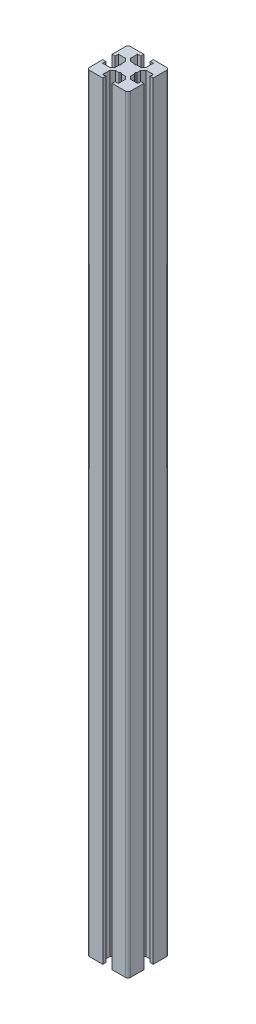
SolidWorks part; units mm, degrees
ref_plane "Front Plane" through (0, 0, 0) normal (0, 0, 1) x (1, 0, 0)
ref_plane "Top Plane" through (0, 0, 0) normal (0, 1, 0) x (1, 0, 0)
ref_plane "Right Plane" through (0, 0, 0) normal (1, 0, 0) x (0, 0, -1)
sketch "Sketch2" plane through (0, 0, 0) normal (0, 1, 0) x (1, 0, 0)
  line L3 (1.7, 7.5) -> (6.5, 7.5)
  line L5 (0, 2.5) -> (-0.5196, 2.8)
  line L6 (-2.85, 3.8) -> (-1.85, 2.8)
  line L9 (1.7, 6.4) -> (1.7, 7.5)
  line L10 (1.7, 6.4) -> (2.85, 6.4)
  line L11 (2.85, 6.4) -> (2.85, 3.8)
  line L12 (2.85, 3.8) -> (1.85, 2.8)
  line L13 (1.85, 2.8) -> (0.5196, 2.8)
  line L14 (2.8, -0.5196) -> (2.8, -1.85)
  line L15 (0, 2.5) -> (0.5196, 2.8)
  line L16 (-2.85, 6.4) -> (-2.85, 3.8)
  line L17 (-1.7, 6.4) -> (-2.85, 6.4)
  line L18 (-1.7, 6.4) -> (-1.7, 7.5)
  line L19 (-1.7, 7.5) -> (-6.5, 7.5)
  line L21 (7.5, -1.7) -> (7.5, -6.5)
  line L22 (6.4, -1.7) -> (7.5, -1.7)
  line L23 (6.4, -1.7) -> (6.4, -2.85)
  line L24 (6.4, -2.85) -> (3.8, -2.85)
  line L25 (2.5, 0) -> (2.8, 0.5196)
  line L26 (0.5196, -2.8) -> (1.85, -2.8)
  line L27 (2.8, 1.85) -> (2.8, 0.5196)
  line L28 (3.8, 2.85) -> (2.8, 1.85)
  line L29 (6.4, 2.85) -> (3.8, 2.85)
  line L30 (6.4, 1.7) -> (6.4, 2.85)
  line L31 (6.4, 1.7) -> (7.5, 1.7)
  line L32 (3.8, -2.85) -> (2.8, -1.85)
  line L33 (2.5, 0) -> (2.8, -0.5196)
  line L34 (7.5, 1.7) -> (7.5, 6.5)
  line L36 (-1.7, -6.4) -> (-1.7, -7.5)
  line L37 (0, -2.5) -> (0.5196, -2.8)
  line L38 (2.85, -3.8) -> (1.85, -2.8)
  line L39 (-1.85, -2.8) -> (-0.5196, -2.8)
  line L41 (0, -2.5) -> (-0.5196, -2.8)
  line L42 (2.85, -6.4) -> (2.85, -3.8)
  line L43 (1.7, -6.4) -> (2.85, -6.4)
  line L44 (1.7, -6.4) -> (1.7, -7.5)
  line L45 (1.7, -7.5) -> (6.5, -7.5)
  line L46 (-1.7, -7.5) -> (-6.5, -7.5)
  line L47 (-1.7, -6.4) -> (-2.85, -6.4)
  line L48 (-2.85, -6.4) -> (-2.85, -3.8)
  line L49 (-2.85, -3.8) -> (-1.85, -2.8)
  line L50 (-7.5, 1.7) -> (-7.5, 6.5)
  line L51 (-6.4, 1.7) -> (-7.5, 1.7)
  line L52 (-6.4, 1.7) -> (-6.4, 2.85)
  line L53 (-6.4, 2.85) -> (-3.8, 2.85)
  line L54 (-2.5, 0) -> (-2.8, -0.5196)
  line L55 (-0.5196, 2.8) -> (-1.85, 2.8)
  line L56 (-2.8, -1.85) -> (-2.8, -0.5196)
  line L57 (-3.8, -2.85) -> (-2.8, -1.85)
  line L58 (-6.4, -2.85) -> (-3.8, -2.85)
  line L59 (-6.4, -1.7) -> (-6.4, -2.85)
  line L60 (-6.4, -1.7) -> (-7.5, -1.7)
  line L61 (-3.8, 2.85) -> (-2.8, 1.85)
  line L62 (-2.5, 0) -> (-2.8, 0.5196)
  line L63 (-7.5, -1.7) -> (-7.5, -6.5)
  line L64 (-2.8, 0.5196) -> (-2.8, 1.85)
  arc A0 (7.5, 6.5) -> (6.5, 7.5) centre (6.5, 6.5) ccw
  arc A1 (-7.5, 6.5) -> (-6.5, 7.5) centre (-6.5, 6.5) cw
  arc A2 (6.5, -7.5) -> (7.5, -6.5) centre (6.5, -6.5) ccw
  arc A3 (-6.5, -7.5) -> (-7.5, -6.5) centre (-6.5, -6.5) cw
  dimension "D11" = 2
  dimension "D2" = 3.4
  dimension "D3" = 5.7
  dimension "D6" = 2.6
  dimension "D7" = 1
  dimension "D8" = 1
extrude "Boss-Extrude1" add sketch "Sketch2" along normal blind 280
